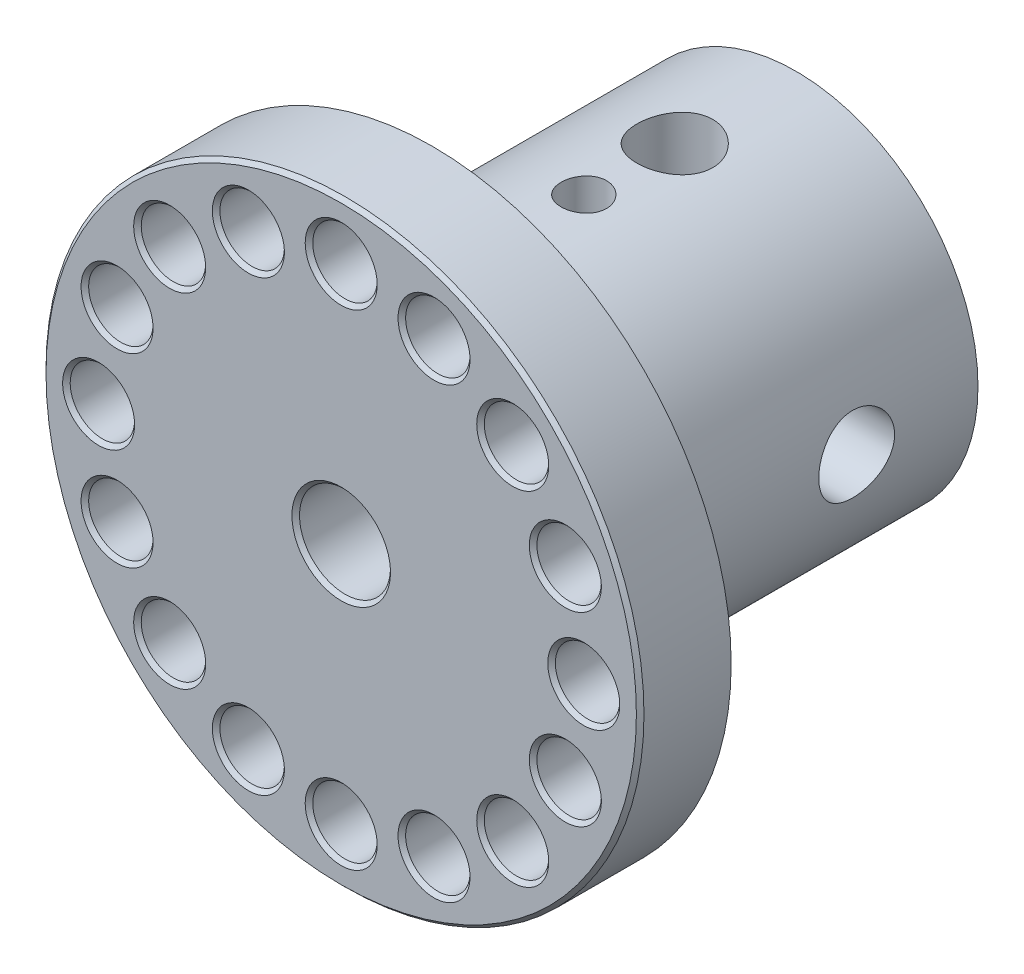
SolidWorks part; units mm, degrees
note: '?' marks a value the reader was unsure of.
ref_plane "Front" through (0, 0, 0) normal (0, 0, 1) x (1, 0, 0)
ref_plane "Top" through (0, 0, 0) normal (0, 1, 0) x (1, 0, 0)
ref_plane "Right" through (0, 0, 0) normal (1, 0, 0) x (0, 0, -1)
sketch "Sketch1" plane through (0, 0, 0) normal (1, 0, 0) x (0, 0, -1)
  line L0 (0, 31.3055) -> (0, 4.7625)
  line L1 (0, 31.3055) -> (9.525, 31.3055)
  line L2 (9.525, 31.3055) -> (9.525, 22.225)
  line L3 (12.7, 19.05) -> (47.625, 19.05)
  line L4 (47.625, 19.05) -> (47.625, 7.0231)
  line L5 (47.625, 7.0231) -> (25.4, 7.0231)
  line L6 (25.4, 7.0231) -> (25.4, 3.9688)
  line L7 (19.05, 4.7625) -> (0, 4.7625)
  line L8 (-8.5328, 0) -> (50.5372, 0) construction
  line L9 (19.05, 4.7625) -> (19.05, 3.9688)
  line L10 (19.05, 3.9688) -> (25.4, 3.9688)
  arc A0 (9.525, 22.225) -> (12.7, 19.05) centre (12.7, 22.225) ccw
  dimension "D1" = 3.175
  dimension "D2" = 9.525
  dimension "D3" = 47.625
  dimension "D4" = 9.525
  dimension "D5" = 14.0462
  dimension "D6" = 38.1
  dimension "D7" = 62.611
  dimension "D8" = 22.225
  dimension "D9" = 7.9375
  dimension "D10" = 19.05
revolve "Base-Revolve" add sketch "Sketch1" angle 360 about L8
ref_axis "Axis1" through (0, 0, -41.4672) along (0, 0, 1)?
sketch "Sketch2" plane through (0, 0, 0) normal (0, 0, 1) x (1, 0, 0)
  circle A0 centre (0, 0) radius 25.4 construction
  circle A1 centre (25.4, 0) radius 3.3734
  dimension "D1" = 50.8
  dimension "D2" = 6.7469
extrude "Cut-Extrude1" cut sketch "Sketch2" against normal through all
pattern_circular "CirPattern1" count 16 every 22.5 about axis through (0, 0, 0) along (0, 0, 1) of "Cut-Extrude1"
sketch "Sketch4" plane through (0, 0, 0) normal (0, 1, 0) x (1, 0, 0)
  line L0 (0, 9.525) -> (0, 0) construction
  line L1 (3.9688, 25.4) -> (-3.9688, 25.4) construction
  circle A0 centre (0, 25.4) radius 2.3813
  dimension "D1" = 4.7625
extrude "Cut-Extrude2" cut sketch "Sketch4" along normal through all
sketch "Sketch3" plane through (0, 0, -47.625) normal (0, 0, -1) x (-1, 0, 0)
  line L0 (-2.54, 9.3599) -> (2.54, 9.3599)
  line L1 (-2.54, 9.3599) -> (-2.54, 6.5477)
  line L2 (2.54, 9.3599) -> (2.54, 6.5477)
  line L3 (0, 0) -> (0, 9.3599) construction
  circle A0 centre (0, 0) radius 7.0231 construction
  arc A1 (2.54, 6.5477) -> (-2.54, 6.5477) centre (0, 0) ccw
  arc A2 (-2.3812, 6.6071) -> (2.3813, 6.6071) centre (0, 0) ccw construction
  dimension "D1" = 16.383
  dimension "D2" = 5.08
extrude "Cut-Extrude3" cut sketch "Sketch3" against normal blind 22.225
sketch "Sketch5" plane through (0, 0, 0) normal (0, 1, 0) x (1, 0, 0)
  line L0 (0, 9.525) -> (0, 0) construction
  line L1 (19.05, 47.625) -> (-19.05, 47.625) construction
  circle A0 centre (0, 34.925) radius 3.9688
  dimension "D1" = 7.9375
  dimension "D2" = 12.7
extrude "Cut-Extrude4" cut sketch "Sketch5" along normal through all
pattern_circular "CirPattern2" count 2 every 90 about axis through (0, 0, -41.4672) along (0, 0, 1) of "Cut-Extrude4"
chamfer "Chamfer1" distance 0.3969 angle 45 18 edges at (11.0111, -26.5832, 0) (20.3459, -20.3459, 0) (26.5832, -11.0111, 0) (4.7625, 0, 0) (31.3055, 0, 0) (28.7734, 0, 0) (26.5832, 11.0111, 0) (20.3459, 20.3459, 0) (11.0111, 26.5832, 0) (0, 28.7734, 0) (-11.0111, 26.5832, 0) (-20.3459, 20.3459, 0) (-26.5832, 11.0111, 0) (-28.7734, 0, 0) (-26.5832, -11.0111, 0) (-20.3459, -20.3459, 0) (-11.0111, -26.5832, 0) (0, -28.7734, 0)
